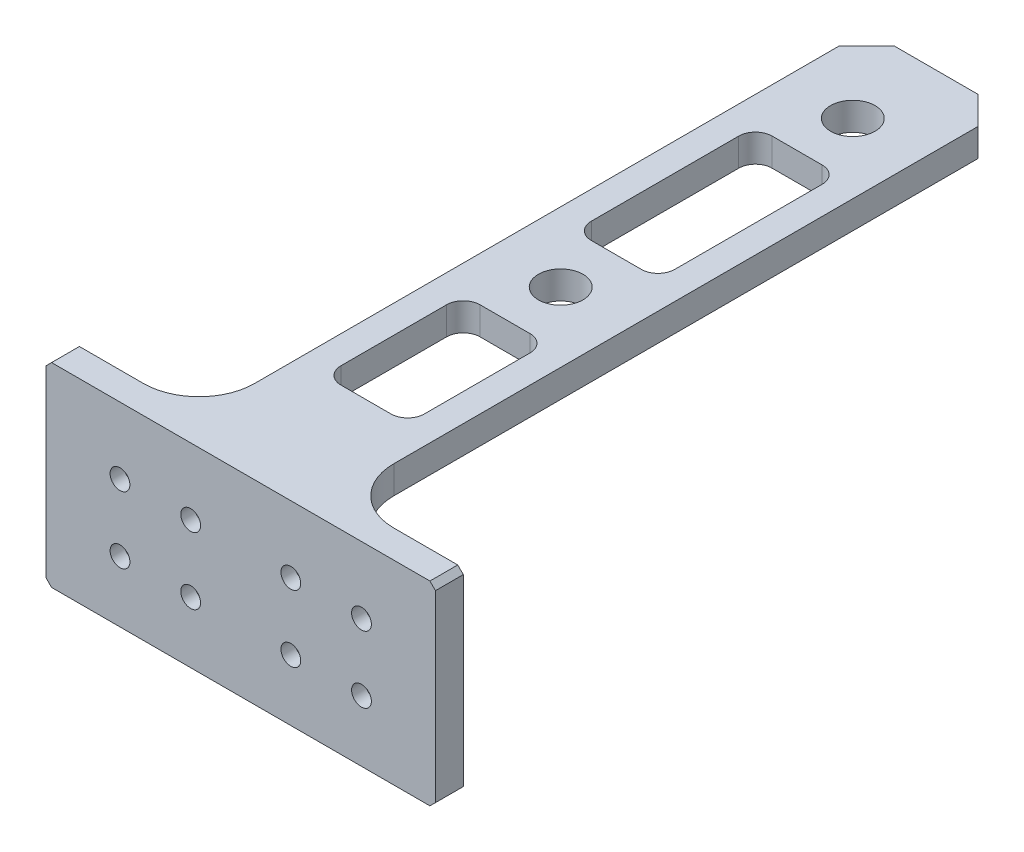
SolidWorks part; units mm, degrees
ref_plane "Front Plane" through (0, 0, 0) normal (0, 0, 1) x (1, 0, 0)
ref_plane "Top Plane" through (0, 0, 0) normal (0, 1, 0) x (1, 0, 0)
ref_plane "Right Plane" through (0, 0, 0) normal (1, 0, 0) x (0, 0, -1)
sketch "Sketch1" plane through (0, 0, 0) normal (0, 1, 0) x (1, 0, 0)
  line L0 (0, 0) -> (0, 23.7757) construction
  line L1 (-12.5, -62.5) -> (12.5, -62.5)
  line L2 (-12.5, -62.5) -> (-12.5, 62.5)
  line L3 (-12.5, 62.5) -> (12.5, 62.5)
  line L4 (12.5, -62.5) -> (12.5, 62.5)
  line L5 (-12.5, -62.5) -> (12.5, 62.5) construction
  line L6 (-12.5, 62.5) -> (12.5, -62.5) construction
  line L7 (-12.5, -62.5) -> (-35, -62.5)
  line L8 (-12.5, -62.5) -> (-12.5, -57.5)
  line L9 (-12.5, -57.5) -> (-35, -57.5)
  line L10 (-35, -62.5) -> (-35, -57.5)
  line L11 (12.5, -62.5) -> (35, -62.5)
  line L12 (12.5, -62.5) -> (12.5, -57.5)
  line L13 (12.5, -57.5) -> (35, -57.5)
  line L14 (35, -62.5) -> (35, -57.5)
  line L17 (0, 0) -> (0, -24.1317) construction
  point P0 (0, 0)
  dimension "D1" = 25
  dimension "D2" = 125
  dimension "D3" = 70
  dimension "D4" = 5
extrude "Boss-Extrude1" add sketch "Sketch1" along normal blind 5 contours L1 L4 L3 L2 | L10 L7 L2 L9 | L11 L14 L13 L4 | L9 L2 | L4 L13 region at (0, 0, 0) region at (-23.75, 0, 60) region at (23.75, 0, 60)
sketch "Sketch2" plane through (0, 5, 0) normal (0, 1, 0) x (1, 0, 0)
  line L0 (0, 0) -> (0, 22.8648) construction
  line L1 (-12.5, 62.5) -> (12.5, 62.5) construction
  line L2 (-35, -62.5) -> (35, -62.5) construction
  circle A0 centre (-7.25, 55) radius 2
  circle A1 centre (7.25, 55) radius 2
  circle A2 centre (-7.25, -40) radius 2
  circle A3 centre (7.25, -40) radius 2
  dimension "D3" = 4
  dimension "D1" = 14.5
  dimension "D2" = 7.5
  dimension "D4" = 22.5
extrude "Cut-Extrude1" [suppressed] cut sketch "Sketch2" against normal through all
chamfer "Chamfer1" distance 5 angle 45 2 edges at (-12.5, 2.5, -62.5) (12.5, 2.5, -62.5)
sketch "Sketch5" plane through (0, 0, 0) normal (0, -1, 0) x (-1, 0, 0)
  line L0 (0, 0) -> (0, 7.4775) construction
  line L2 (-35, -57.5) -> (35, -57.5)
  line L3 (-35, -57.5) -> (-35, -62.5)
  line L4 (-35, -62.5) -> (35, -62.5)
  line L5 (35, -57.5) -> (35, -62.5)
  line L6 (-2.5, -57.5) -> (2.5, -57.5)
  line L7 (-2.5, -57.5) -> (-2.5, -42.5)
  line L8 (-2.5, -42.5) -> (2.5, -42.5)
  line L9 (2.5, -57.5) -> (2.5, -42.5)
  line M14 (-12.5, -57.5) -> (-35, -57.5)
  line M15 (-35, -57.5) -> (-35, -62.5)
  line M16 (-35, -62.5) -> (35, -62.5)
  line M17 (35, -62.5) -> (35, -57.5)
  line M18 (35, -57.5) -> (12.5, -57.5)
  dimension "D1" = 5
  dimension "D2" = 15
extrude "Boss-Extrude3" add sketch "Sketch5" along normal blind 30 contours L2 L9 L8 L7 | L2 M14 M15 M16 M17 M18 region at (0, 0, 60) region at (0, 0, 50)
hole_wizard "Hole1" positions "Sketch8" profile "Sketch7" legacy end condition through all
sketch "Sketch8" plane through (0, 0, 57.5) normal (0, 0, -1) x (-1, 0, 0)
  line L0 (0, 0) -> (0, -8.6827) construction
  line L2 (-21.7, -7) -> (-9, -7) construction
  line L3 (-15.35, -7) -> (-15.35, -4.1308) construction
  line L10 (-12.5, 5) -> (-35, 5) construction
  point P0 (-21.7, -7)
  point P2 (-9, -7)
  point P4 (9, -7)
  point P6 (21.7, -7)
  point P43 (-9, -19)
  point P45 (-21.7, -19)
  point P47 (9, -19)
  point P49 (21.7, -19)
  dimension "D1" = 12.7
  dimension "D2" = 18
  dimension "D3" = 12
  dimension "D4" = 12
  dimension "D5" = 12.7
  dimension "D6" = 12.7
  dimension "D7" = 12
sketch "Sketch7" plane through (21.7, -7, 57.5) normal (1, 0, 0) x (0, 1, 0)
  line L0 (0, 0) -> (0, 5)
  line L1 (0, 5) -> (1.778, 5)
  line L2 (1.778, 5) -> (1.778, 2.54)
  line L3 (1.778, 2.54) -> (3.429, 2.54)
  line L4 (3.429, 2.54) -> (3.429, 0)
  line L5 (3.429, 0) -> (0, 0)
  line L6 (0, 110) -> (0, -10) construction
  dimension "Diameter" = 3.556
  dimension "Depth" = 5
  dimension "C-Bore Diameter" = 6.858
  dimension "C-Bore Depth" = 2.54
sketch "Sketch9" plane through (0, 0, 0) normal (0, -1, 0) x (1, 0, 0)
  line L0 (-7.5, -62.5) -> (7.5, -62.5) construction
  circle A0 centre (0, -47.5) radius 4
  circle A1 centre (0, 5) radius 4
  circle A2 centre (0, 5) radius 30 construction
  circle A3 centre (0, -47.5) radius 22.5 construction
  dimension "D1" = 8
  dimension "D3" = 60
  dimension "D4" = 45
  dimension "D2" = 52.5
  dimension "D5" = 15
extrude "Cut-Extrude2" cut sketch "Sketch9" against normal through all
sketch "Sketch10" plane through (0, 0, 0) normal (0, -1, 0) x (1, 0, 0)
  line L0 (12.5, 57.5) -> (12.5, -57.5) construction
  line L1 (-7.5, -37.5) -> (7.5, -37.5)
  line L2 (-7.5, -37.5) -> (-7.5, -5)
  line L3 (-7.5, -5) -> (7.5, -5)
  line L4 (7.5, -37.5) -> (7.5, -5)
  line L5 (-7.5, -37.5) -> (7.5, -5) construction
  line L6 (-7.5, -5) -> (7.5, -37.5) construction
  line L7 (0, 0) -> (0, -30.917) construction
  circle A0 centre (0, 5) radius 4 construction
  circle A1 centre (0, -47.5) radius 4 construction
  point P0 (0, -21.25)
  dimension "D3" = 10
  dimension "D1" = 5
  dimension "D2" = 10
extrude "Cut-Extrude3" cut sketch "Sketch10" against normal through all
sketch "Sketch12" plane through (-2.5, 0, 0) normal (-1, 0, 0) x (0, 0, 1)
  line L0 (50, -5) -> (50, -25) construction
  line L1 (51.5, -5) -> (51.5, -25)
  line L2 (48.5, -5) -> (48.5, -25)
  line L4 (42.5, -27.9894) -> (57.5, -27.9894) construction
  line L5 (42.5, -30) -> (42.5, 0) construction
  line L6 (57.5, 5) -> (57.5, -30) construction
  line L7 (50, -27.9894) -> (50, -38.5033) construction
  line L8 (57.5, -30) -> (42.5, -30) construction
  arc A0 (51.5, -5) -> (48.5, -5) centre (50, -5) ccw
  arc A1 (48.5, -25) -> (51.5, -25) centre (50, -25) ccw
  point P2 (50, -15)
  dimension "D1" = 1.5
  dimension "D2" = 20
  dimension "D3" = 5
extrude "Cut-Extrude4" cut sketch "Sketch12" against normal through all
fillet "Fillet5" radius 10 2 edges at (-12.5, 2.5, 57.5) (12.5, 2.5, 57.5)
sketch "Sketch13" plane through (0, 0, 0) normal (0, -1, 0) x (1, 0, 0)
  line L0 (-7.5, -5) -> (-7.5, -37.5) construction
  line L1 (-7.5, 15) -> (7.5, 15)
  line L2 (-7.5, 15) -> (-7.5, 40)
  line L3 (-7.5, 40) -> (7.5, 40)
  line L4 (7.5, 15) -> (7.5, 40)
  line L5 (-7.5, 15) -> (7.5, 40) construction
  line L6 (-7.5, 40) -> (7.5, 15) construction
  line L7 (7.5, -37.5) -> (7.5, -5) construction
  circle A0 centre (0, 5) radius 4 construction
  point P0 (0, 27.5)
  dimension "D1" = 25
  dimension "D2" = 10
extrude "Cut-Extrude5" cut sketch "Sketch13" against normal through all
fillet "Fillet3" radius 3 8 edges at (7.5, 2.5, -5) (-7.5, 2.5, -5) (-7.5, 2.5, -37.5) (7.5, 2.5, -37.5) (-7.5, 2.5, 15) (-7.5, 2.5, 40) (7.5, 2.5, 40) (7.5, 2.5, 15)
chamfer "Chamfer3" distance 1 angle 45 5 edges at (35, 5, 60) (-35, 5, 60) (35, -30, 60) (-35, -30, 60) (0, -30, 42.5)
